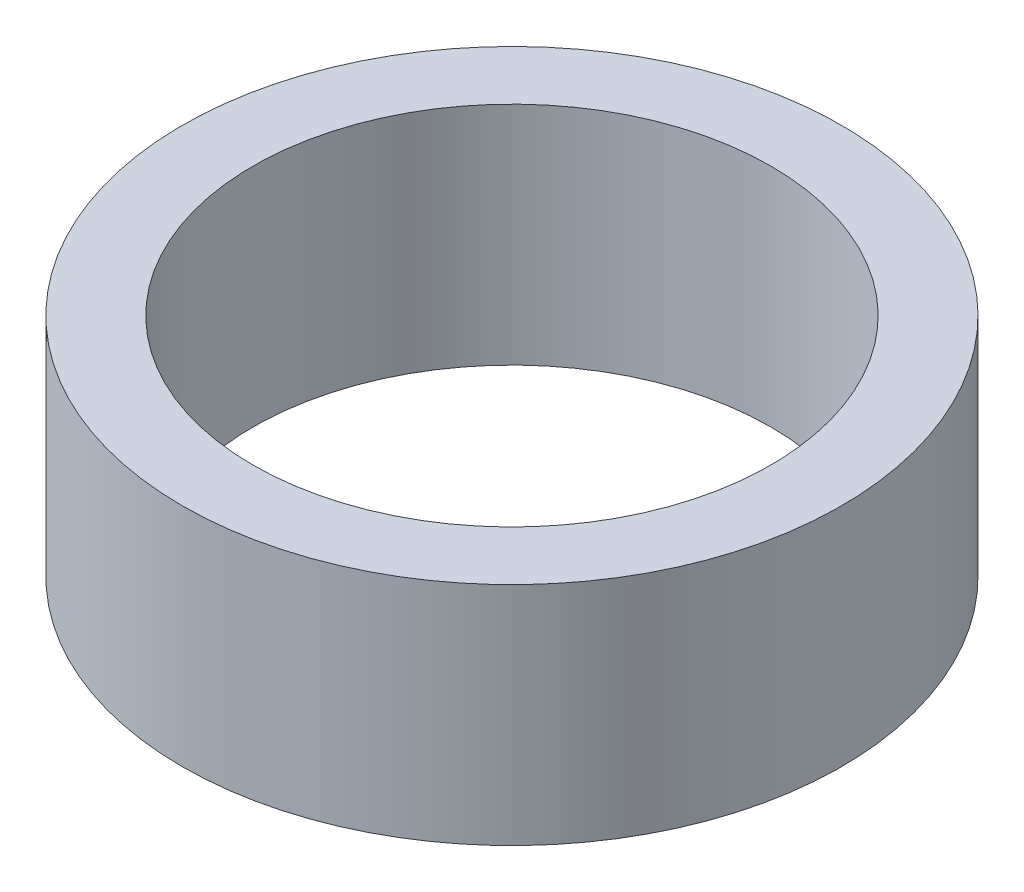
SolidWorks part; units mm, degrees
ref_plane "Front Plane" through (0, 0, 0) normal (0, 0, 1) x (1, 0, 0)
ref_plane "Top Plane" through (0, 0, 0) normal (0, 1, 0) x (1, 0, 0)
ref_plane "Right Plane" through (0, 0, 0) normal (1, 0, 0) x (0, 0, -1)
sketch "Sketch1" plane through (0, 0, 0) normal (0, 1, 0) x (1, 0, 0)
  circle A0 centre (0, 0) radius 35
  dimension "FLANGE_OD" = 70
extrude "Boss-Extrude1" add sketch "Sketch1" along normal blind 24
sketch "Sketch2" plane through (0, 0, 0) normal (0, 1, 0) x (1, 0, 0)
  circle A0 centre (0, 0) radius 27.5
  dimension "BORE_D" = 55
extrude "Cut-Extrude1" cut sketch "Sketch2" along normal through all
sketch "Sketch3" plane through (0, 24, 0) normal (0, 1, 0) x (1, 0, 0)
  circle A0 centre (0, 0) radius 15.8968 construction
  circle A1 centre (-15.8968, 0) radius 1.5
  dimension "BOLT_D" = 3
  dimension "BOLT_PCD" = 31.7937
extrude "Cut-Extrude2" cut sketch "Sketch3" against normal blind 21.3076 rebuild error yes
pattern_circular "CirPattern1" count 6 over 360 rebuild error yes
